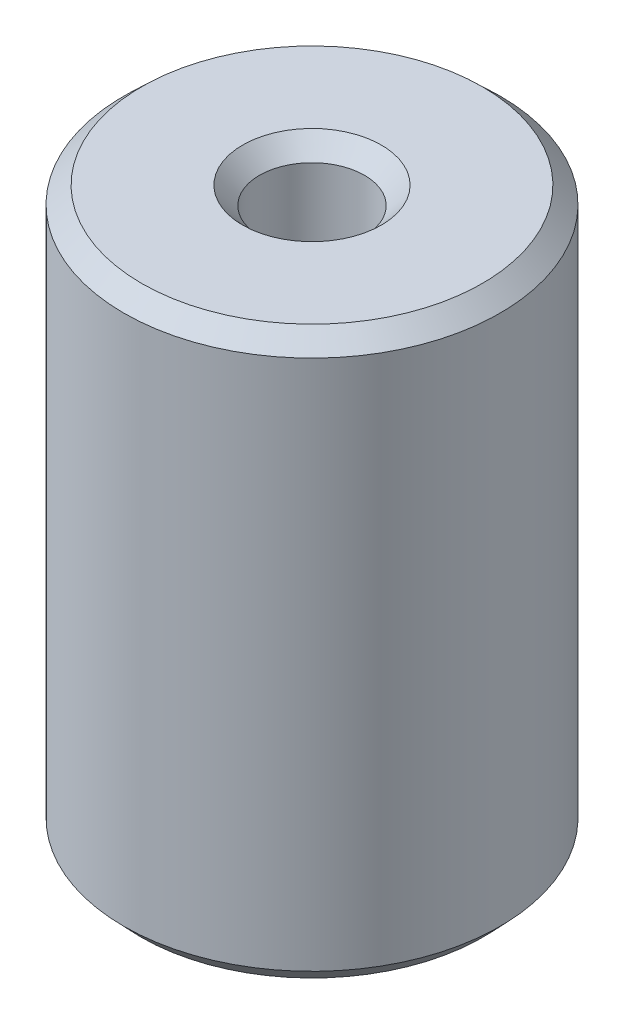
SolidWorks part; units mm, degrees
ref_plane "Front Plane" through (0, 0, 0) normal (0, 0, 1) x (1, 0, 0)
ref_plane "Top Plane" through (0, 0, 0) normal (0, 1, 0) x (1, 0, 0)
ref_plane "Right Plane" through (0, 0, 0) normal (1, 0, 0) x (0, 0, -1)
sketch "Sketch1" plane through (0, 0, 0) normal (0, 1, 0) x (1, 0, 0)
  circle A0 centre (0, 0) radius 5
  dimension "SLEEVE_OD" = 10
extrude "Boss-Extrude1" add sketch "Sketch1" along normal blind 15.0362
sketch "Sketch2" plane through (0, 0, 0) normal (0, 1, 0) x (1, 0, 0)
  circle A0 centre (0, 0) radius 1.3955
  dimension "BORE_D" = 2.7909
extrude "Cut-Extrude1" cut sketch "Sketch2" along normal through all
chamfer "Chamfer1" distance 0.4488 angle 46.395 4 edges at (0, 15.0362, 1.3955) (0, 0, 1.3955) (0, 0, 5) (0, 15.0362, 5) first distance on face at (0, 15.0362, 1.3955) first distance on face at (0, 0, 1.3955) first distance on face at (0, 15.0362, 5)
